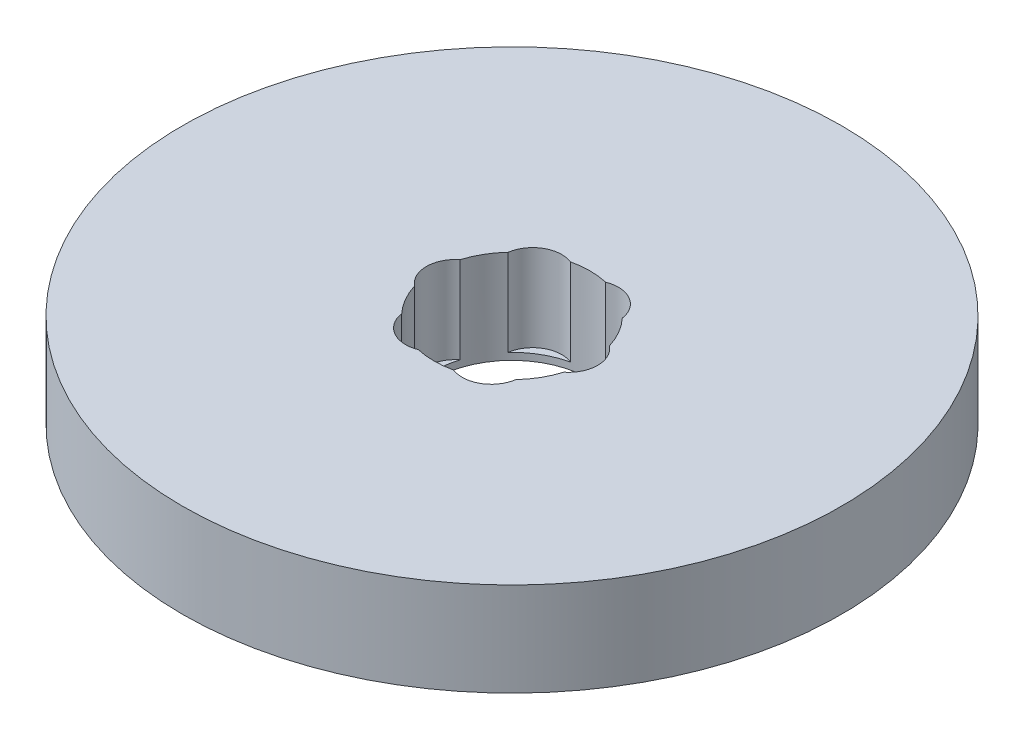
SolidWorks part; units mm, degrees
ref_plane "Front Plane" through (0, 0, 0) normal (0, 0, 1) x (1, 0, 0)
ref_plane "Top Plane" through (0, 0, 0) normal (0, 1, 0) x (1, 0, 0)
ref_plane "Right Plane" through (0, 0, 0) normal (1, 0, 0) x (0, 0, -1)
sketch "Sketch1" plane through (0, 0, 0) normal (0, 1, 0) x (1, 0, 0)
  circle A0 centre (0, 0) radius 95
  dimension "FLANGE_OD" = 190
extrude "Boss-Extrude1" add sketch "Sketch1" along normal blind 27
sketch "Sketch2" plane through (0, 0, 0) normal (0, 1, 0) x (1, 0, 0)
  circle A0 centre (0, 0) radius 22.5
  dimension "BORE_D" = 45
extrude "Cut-Extrude1" cut sketch "Sketch2" along normal through all
sketch "Sketch3" plane through (0, 27, 0) normal (0, 1, 0) x (1, 0, 0)
  circle A0 centre (0, 0) radius 16.3091 construction
  circle A1 centre (-16.3091, 0) radius 8.3868
  dimension "BOLT_D" = 16.7736
  dimension "BOLT_PCD" = 32.6182
extrude "Cut-Extrude2" cut sketch "Sketch3" against normal blind 24.9947
pattern_circular "CirPattern1" count 6 over 360 about axis through (0, 0, 0) along (0, 1, 0) of "Cut-Extrude2"
